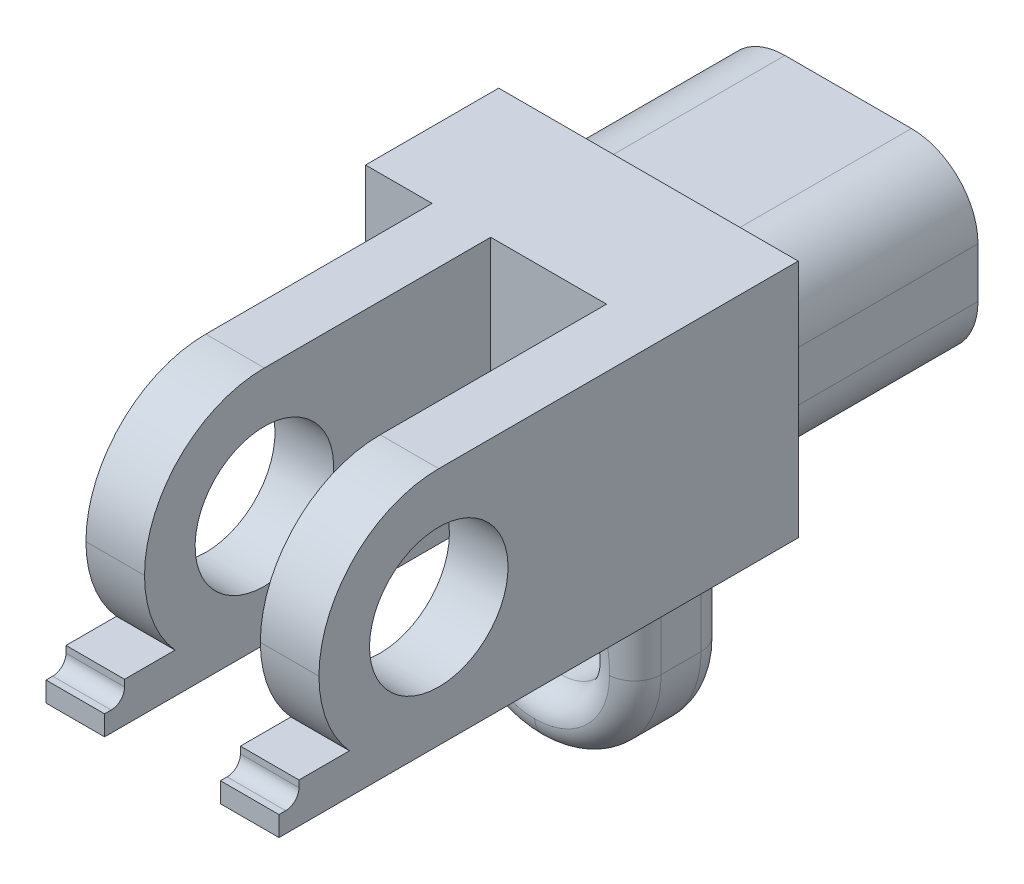
SolidWorks part; units mm, degrees
ref_plane "Plan de face" through (0, 0, 0) normal (0, 0, 1) x (1, 0, 0)
ref_plane "Plan de dessus" through (0, 0, 0) normal (0, 1, 0) x (1, 0, 0)
ref_plane "Plan de droite" through (0, 0, 0) normal (1, 0, 0) x (0, 0, -1)
sketch "Sketch2" plane through (0, 0, 0) normal (0, 0, 1) x (1, 0, 0)
  line L1 (12.3825, -8.7312) -> (-12.3825, -8.7312)
  line L2 (12.3825, -8.7312) -> (12.3825, 8.7313)
  line L3 (12.3825, 8.7313) -> (-12.3825, 8.7312)
  line L4 (-12.3825, -8.7312) -> (-12.3825, 8.7312)
  line L5 (12.3825, -8.7312) -> (-12.3825, 8.7312) construction
  line L6 (12.3825, 8.7313) -> (-12.3825, -8.7312) construction
  point P0 (0, 0)
  dimension "D1" = 24.765
  dimension "D2" = 17.4625
extrude "Boss-Extrude1" add sketch "Sketch2" against normal blind 19.05
sketch "Sketch3" plane through (0, 0, 0) normal (0, 0, 1) x (1, 0, 0)
  line L1 (14.2875, -11.43) -> (-14.2875, -11.43)
  line L2 (14.2875, -11.43) -> (14.2875, 11.43)
  line L3 (14.2875, 11.43) -> (-14.2875, 11.43)
  line L4 (-14.2875, -11.43) -> (-14.2875, 11.43)
  line L5 (14.2875, -11.43) -> (-14.2875, 11.43) construction
  line L6 (14.2875, 11.43) -> (-14.2875, -11.43) construction
  point P0 (0, 0)
  dimension "D1" = 28.575
  dimension "D2" = 22.86
extrude "Boss-Extrude2" add sketch "Sketch3" along normal blind 45.72
sketch "Sketch4" plane through (0, -11.43, 0) normal (0, -1, 0) x (-1, 0, 0)
  line L0 (14.2875, -45.72) -> (-14.2875, -45.72) construction
  line L1 (14.2875, -45.72) -> (7.9375, -45.72)
  line L2 (14.2875, -45.72) -> (14.2875, -12.7)
  line L3 (14.2875, -12.7) -> (7.9375, -12.7)
  line L4 (7.9375, -45.72) -> (7.9375, -12.7)
  line L5 (2.3495, -45.72) -> (-8.6995, -45.72)
  line L6 (2.3495, -45.72) -> (2.3495, -12.7)
  line L7 (2.3495, -12.7) -> (-8.6995, -12.7)
  line L8 (-8.6995, -45.72) -> (-8.6995, -12.7)
  line L9 (-14.2875, -45.72) -> (-14.2875, 0) construction
  dimension "D1" = 33.02
  dimension "D2" = 33.02
  dimension "D3" = 6.35
  dimension "D4" = 5.588
  dimension "D5" = 5.588
extrude "Cut-Extrude1" cut sketch "Sketch4" against normal through all
sketch "Sketch5" plane through (0, -11.43, 0) normal (0, -1, 0) x (1, 0, 0)
  line L0 (-14.2875, 0) -> (14.2875, 0) construction
  line L1 (-9.525, 10.8585) -> (9.525, 10.8585)
  line L2 (-9.525, 10.8585) -> (-9.525, 1.9685)
  line L3 (-9.525, 1.9685) -> (9.525, 1.9685)
  line L4 (9.525, 10.8585) -> (9.525, 1.9685)
  line L5 (-14.2875, 12.7) -> (-14.2875, 0) construction
  point P6 (-9.525, 6.4135)
  dimension "D1" = 8.89
  dimension "D2" = 1.9685
  dimension "D3" = 19.05
  dimension "D4" = 4.7625
extrude "Boss-Extrude3" add sketch "Sketch5" along normal blind 19.05
fillet "Fillet1" radius 9.525 2 edges at (9.525, -30.48, 6.4135) (-9.525, -30.48, 6.4135)
sketch "Sketch6" plane through (0, 0, 1.9685) normal (0, 0, -1) x (-1, 0, 0)
  line L0 (0, -20.955) -> (0, -11.43) construction
  line L1 (9.525, -11.43) -> (-9.525, -11.43) construction
  line L2 (0, -20.955) -> (0, -30.48) construction
  circle A1 centre (0, -20.955) radius 4.7625
  dimension "D1" = 9.525
extrude "Cut-Extrude2" cut sketch "Sketch6" against normal through all
fillet "Fillet5" radius 11.43 4 edges at (-5.1435, -11.43, 45.72) (-5.1435, 11.43, 45.72) (11.4935, 11.43, 45.72) (11.4935, -11.43, 45.72)
sketch "Sketch7" plane through (-7.9375, 0, 0) normal (-1, 0, 0) x (0, 0, 1)
  circle A1 centre (34.29, 0) radius 6.604
  dimension "D1" = 13.208
extrude "Cut-Extrude3" cut sketch "Sketch7" against normal through all
fillet "Fillet2" radius 2.54 10 edges at (-4.7625, -20.955, 1.9685) (-4.7625, -20.955, 10.8585) (9.525, -16.1925, 1.9685) (-9.525, -16.1925, 1.9685) (-6.7352, -27.6902, 1.9685) (-9.525, -16.1925, 10.8585) (-6.7352, -27.6902, 10.8585) (9.525, -16.1925, 10.8585) (6.7352, -27.6902, 1.9685) (6.7352, -27.6902, 10.8585)
fillet "Fillet3" radius 6.35 4 edges at (-12.3825, -8.7312, -9.525) (-12.3825, 8.7312, -9.525) (12.3825, -8.7312, -9.525) (12.3825, 8.7313, -9.525)
sketch "Sketch14" plane through (14.2875, 0, 0) normal (1, 0, 0) x (0, 0, -1)
  line L0 (-34.29, -11.43) -> (-49.53, -11.43)
  line L1 (-49.53, -11.43) -> (-49.53, -7.62)
  line L2 (-49.53, -7.62) -> (-42.8094, -7.62)
  line L3 (-42.8094, -7.62) -> (-34.29, -11.43)
  arc A0 (-45.72, 0) -> (-34.29, -11.43) centre (-34.29, 0) ccw construction
  dimension "D1" = 15.24
  dimension "D2" = 3.81
extrude "Boss-Extrude5" add sketch "Sketch14" against normal blind 5.588
sketch "Sketch16" plane through (-7.9375, 0, 0) normal (-1, 0, 0) x (0, 0, 1)
  line L2 (42.8094, -7.62) -> (34.29, -11.43)
  line L4 (42.8094, -7.62) -> (49.53, -7.62)
  line L5 (49.53, -7.62) -> (49.53, -11.43)
  line L6 (49.53, -11.43) -> (34.29, -11.43)
  dimension "D1" = 15.24
extrude "Boss-Extrude6" add sketch "Sketch16" against normal blind 5.588
sketch "Sketch17" plane through (-7.9375, 0, 0) normal (-1, 0, 0) x (0, 0, 1)
  line L6 (49.53, -7.62) -> (49.53, -9.525)
  line L7 (49.53, -11.43) -> (49.53, -7.62) construction
  line L8 (49.53, -9.525) -> (47.625, -9.525)
  line L9 (47.625, -9.525) -> (47.625, -7.62)
  line L10 (49.53, -7.62) -> (42.8094, -7.62) construction
  line L11 (47.625, -7.62) -> (49.53, -7.62)
  dimension "D1" = 1.905
  dimension "D2" = 1.905
extrude "Cut-Extrude9" cut sketch "Sketch17" against normal through all
fillet "Fillet6" radius 1.27 2 edges at (11.4935, -9.525, 47.625) (-5.1435, -9.525, 47.625)
